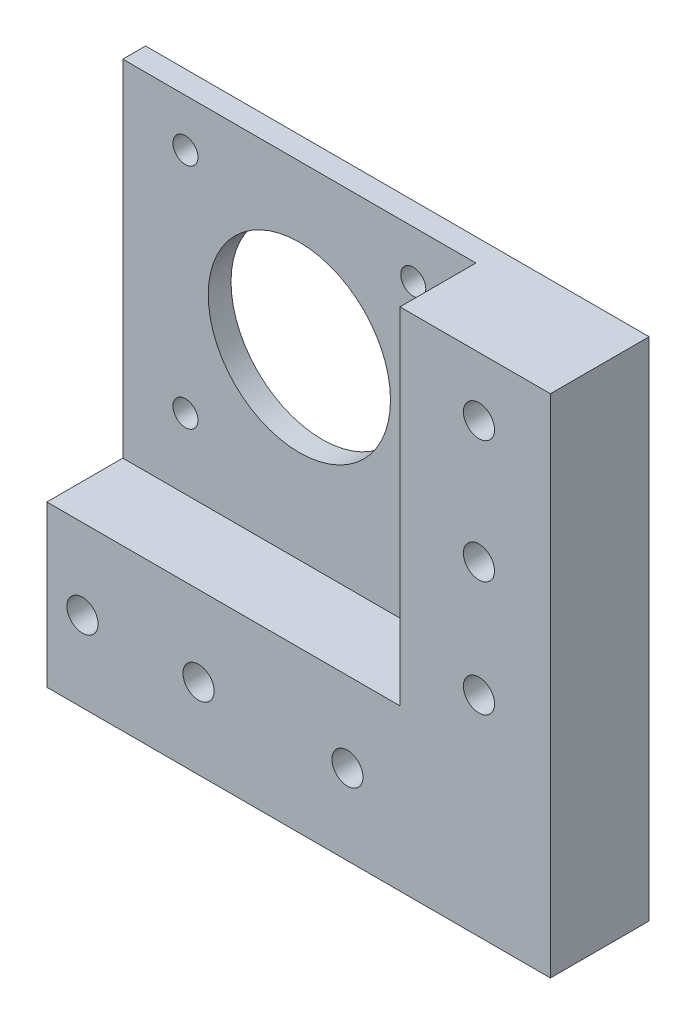
SolidWorks part; units mm, degrees
ref_plane "Front Plane" through (0, 0, 0) normal (0, 0, 1) x (1, 0, 0)
ref_plane "Top Plane" through (0, 0, 0) normal (0, 1, 0) x (1, 0, 0)
ref_plane "Right Plane" through (0, 0, 0) normal (1, 0, 0) x (0, 0, -1)
sketch "Sketch1" plane through (0, 0, 0) normal (0, 1, 0) x (1, 0, 0)
  line L0 (46.5, 40) -> (46.5, 0)
  line L1 (46.5, 0) -> (0, 0)
  line L2 (0, 40) -> (46.5, 40)
  line L10 (0, 0) -> (0, 40)
  dimension "D1" = 40
  dimension "D2" = 46.5
extrude "Boss-Extrude1" add sketch "Sketch1" along normal blind 3 contours L10 L1 L0 L2 region at (23.25, 0, -20)
sketch "Sketch2" plane through (0, 3, 0) normal (0, 1, 0) x (1, 0, 0)
  line L4 (2, 40) -> (2, 0)
  line L5 (0, 40) -> (0, 0)
  line L6 (0, 0) -> (46.5, 0)
  line L7 (0, 40) -> (0, 0)
  line L8 (46.5, 40) -> (46.5, 0)
  line L9 (46.5, 0) -> (46.5, 40)
  line L10 (44.5, 40) -> (44.5, 0)
  line L11 (2, 2.5) -> (44.5, 2.5)
  line L12 (46.5, 40) -> (0, 40)
  line L13 (0, 40) -> (0, 0)
  line L14 (0, 0) -> (46.5, 0)
  line L15 (46.5, 0) -> (46.5, 40)
  line L16 (46.5, 40) -> (0, 40)
  dimension "D2" = 2
  dimension "D3" = 42.5
  dimension "D4" = 0
  dimension "D1" = 2.5
extrude "Boss-Extrude2" add sketch "Sketch2" along normal blind 42.5 contours L10 L8 | L11 L4 L10 | L7 L4 region at (1, 3, -20) region at (23.25, 3, -1.25) region at (45.5, 3, -20)
sketch "Sketch4" plane through (0, 0, 0) normal (0, 0, 1) x (1, 0, 0)
  line L0 (2, 45.5) -> (44.5, 3) construction
  line L1 (44.5, 45.5) -> (2, 3) construction
  line L8 (2, 3) -> (44.5, 3)
  line L9 (2, 45.5) -> (2, 3)
  line L10 (44.5, 45.5) -> (2, 45.5)
  line L11 (44.5, 3) -> (44.5, 45.5)
  line L12 (2, 3) -> (44.5, 3)
  line L13 (2, 45.5) -> (2, 3)
  line L14 (44.5, 45.5) -> (2, 45.5)
  line L15 (44.5, 3) -> (44.5, 45.5)
  line L16 (2, 3) -> (44.5, 3)
  line L17 (2, 45.5) -> (2, 3)
  line L18 (44.5, 45.5) -> (2, 45.5)
  line L19 (44.5, 3) -> (44.5, 45.5)
  circle A0 centre (23.25, 24.25) radius 12
  circle A1 centre (8.25, 39.25) radius 1.65
  circle A2 centre (8.25, 9.25) radius 1.65
  circle A3 centre (38.25, 9.25) radius 1.65
  circle A4 centre (38.25, 39.25) radius 1.65
  dimension "D2" = 24
  dimension "D3" = 3.3
  dimension "D4" = 30
  dimension "D1" = 0
extrude "Cut-Extrude2" cut sketch "Sketch4" against normal through all contours A0 | A2 | A1 | A4 | A3 region at (23.25, 24.25, 0)
sketch "Sketch7" plane through (0, 0, 0) normal (0, 0, 1) x (1, 0, 0)
  line L0 (46.5, -21.1336) -> (66.3113, -21.1336)
  line L1 (46.5, 45.5) -> (66.3113, 45.5)
  line L2 (46.5, 45.5) -> (46.5, 0)
  line L3 (46.5, 0) -> (66.3113, 0)
  line L4 (0, 0) -> (46.5, 0)
  line L5 (46.5, 0) -> (46.5, 45.5)
  line L6 (46.5, 45.5) -> (0, 45.5)
  line L7 (0, 45.5) -> (0, 0)
  line L8 (0, 0) -> (46.5, 0)
  line L9 (46.5, 0) -> (46.5, 45.5)
  line L10 (46.5, 45.5) -> (0, 45.5)
  line L11 (0, 45.5) -> (0, 0)
  line L12 (66.3113, 45.5) -> (66.3113, 0)
  line L13 (46.5, 0) -> (0, 0)
  line L14 (46.5, 0) -> (46.5, -21.1336)
  line L15 (46.5, -21.1336) -> (0, -21.1336)
  line L16 (0, 0) -> (0, -21.1336)
  line L17 (66.3113, -21.1336) -> (66.3113, 0)
  circle A0 centre (56.9031, 37.7216) radius 2.05
  circle A1 centre (56.9031, 6.4297) radius 2.05
  circle A2 centre (56.9031, 21.6094) radius 2.05
  circle A3 centre (39.5824, -10.5668) radius 2.05
  circle A4 centre (4.6913, -10.5668) radius 2.05
  circle A5 centre (19.9769, -10.5668) radius 2.05
  circle M5 centre (8.25, 9.25) radius 1.65
  circle M6 centre (8.25, 39.25) radius 1.65
  circle M7 centre (38.25, 39.25) radius 1.65
  circle M8 centre (38.25, 9.25) radius 1.65
  circle M9 centre (23.25, 24.25) radius 12
  line M10 (0, 0) -> (46.5, 0)
  line M11 (46.5, 0) -> (46.5, 45.5)
  line M12 (46.5, 45.5) -> (0, 45.5)
  line M13 (0, 45.5) -> (0, 0)
  dimension "D2" = 4.1
  dimension "D1" = 0
extrude "Boss-Extrude3" add sketch "Sketch7" against normal blind 3 contours L12 L1 L3 A2 A1 A0 M11 | L16 L15 L14 A5 A4 A3 M10 | M13 M10 M11 M12 M6 M8 M9 M7 M5 region at (23.327, -10.5668, 0) region at (23.25, 0.6506, 0) region at (46.9963, 22.75, 0)
extrude "Boss-Extrude8" add sketch "Sketch7<6>" along normal blind 10 and the other way blind 3 contours L0 L17 L3 L14 | L12 L1 L3 A2 A1 A0 M11 | L16 L15 L14 A5 A4 A3 M10 region at (56.4056, -10.5668, 0) region at (23.327, -10.5668, 0) region at (46.9963, 22.75, 0)
sketch "Sketch7<6>" plane through (0, 0, 0) normal (0, 0, 1) x (1, 0, 0) same geometry as "Sketch7"
sketch "Sketch8" plane through (0, 0, -3) normal (0, 0, -1) x (-1, 0, 0)
  line L0 (-2, 45.5) -> (-44.5, 45.5) construction
  line L1 (-44.5, 45.5) -> (-44.5, 3) construction
  line L2 (-44.5, 3) -> (-2, 3) construction
  line L3 (-2, 3) -> (-2, 45.5) construction
  line L4 (0, -21.1336) -> (0, 0) construction
  line L5 (0, 0) -> (-46.5, 0) construction
  line L6 (-46.5, 0) -> (-46.5, 45.5) construction
  line L7 (-46.5, 45.5) -> (-66.3113, 45.5) construction
  line L8 (-66.3113, 45.5) -> (-66.3113, -21.1336) construction
  line L9 (-66.3113, -21.1336) -> (0, -21.1336) construction
  line L10 (-2, 45.5) -> (-44.5, 45.5)
  line L11 (-44.5, 45.5) -> (-44.5, 3)
  line L12 (-44.5, 3) -> (-2, 3)
  line L13 (-2, 3) -> (-2, 45.5)
  line L14 (0, -21.1336) -> (0, 0)
  line L15 (0, 0) -> (-46.5, 0)
  line L16 (-46.5, 0) -> (-46.5, 45.5)
  line L17 (-46.5, 45.5) -> (-66.3113, 45.5)
  line L18 (-66.3113, 45.5) -> (-66.3113, -21.1336)
  line L19 (-66.3113, -21.1336) -> (0, -21.1336)
  line L28 (-46.5, 0) -> (0, 0)
  line L29 (0, 0) -> (0, 45.5)
  line L30 (0, 45.5) -> (-2, 45.5)
  line L31 (-2, 45.5) -> (-2, 3)
  line L32 (-2, 3) -> (-44.5, 3)
  line L33 (-44.5, 3) -> (-44.5, 45.5)
  line L34 (-44.5, 45.5) -> (-46.5, 45.5)
  line L35 (-46.5, 45.5) -> (-46.5, 0)
  line L36 (-46.5, 0) -> (0, 0)
  line L37 (0, 0) -> (0, 45.5)
  line L38 (0, 45.5) -> (-2, 45.5)
  line L39 (-2, 45.5) -> (-2, 3)
  line L40 (-2, 3) -> (-44.5, 3)
  line L41 (-44.5, 3) -> (-44.5, 45.5)
  line L42 (-44.5, 45.5) -> (-46.5, 45.5)
  line L43 (-46.5, 45.5) -> (-46.5, 0)
  line M13 (0, 0) -> (-46.5, 0)
  line M14 (-46.5, 0) -> (-46.5, 45.5)
  dimension "D1" = 0
extrude "Cut-Extrude4" cut sketch "Sketch8" along normal up to surface (37 mm away) contours L11 L42 L37 L38 L13 L12 M14 M13 region at (1, 44.8494, -3) up to face at (23.25, 23.5, -40)
